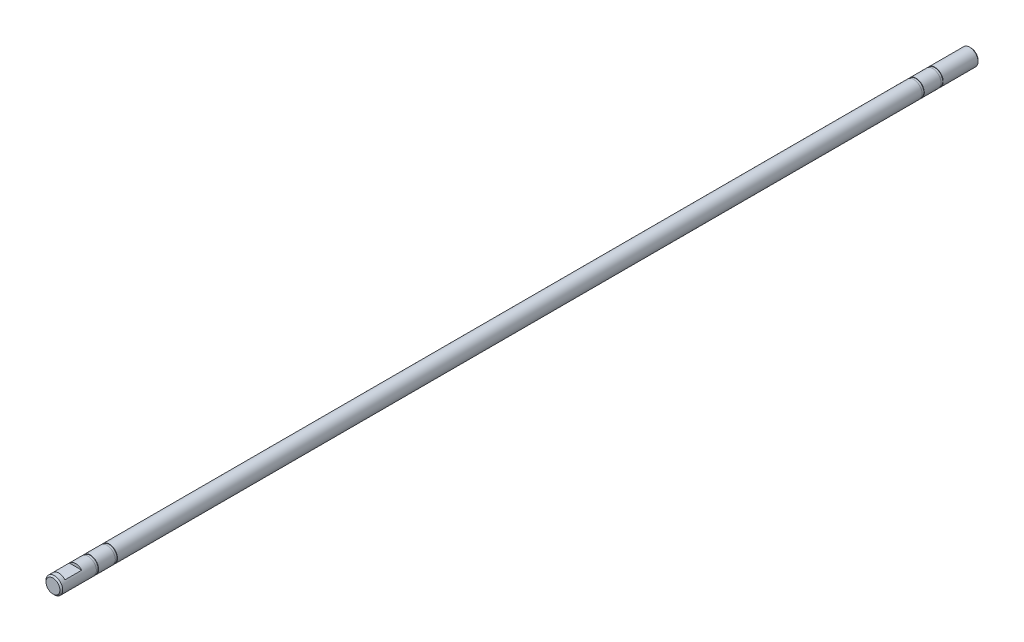
SolidWorks part; units mm, degrees
ref_plane "Front Plane" through (0, 0, 0) normal (0, 0, 1) x (1, 0, 0)
ref_plane "Top Plane" through (0, 0, 0) normal (0, 1, 0) x (1, 0, 0)
ref_plane "Right Plane" through (0, 0, 0) normal (1, 0, 0) x (0, 0, -1)
sketch "Sketch1" plane through (0, 0, 0) normal (0, 0, 1) x (1, 0, 0)
  circle A0 centre (0, 0) radius 3
  dimension "D1" = 6
extrude "Boss-Extrude1" add sketch "Sketch1" along normal blind 330
sketch "Sketch2" plane through (0, 0, 0) normal (0, 0, -1) x (-1, 0, 0)
  circle A0 centre (0, 0) radius 2.85
  circle A1 centre (0, 0) radius 3 construction
  circle A2 centre (0, 0) radius 3
  dimension "D1" = 5.7
extrude "Cut-Extrude1" cut sketch "Sketch2" against normal blind 0.8 from offset 13 offset against normal yes
sketch "Sketch3" plane through (0, 0, 13.8) normal (0, 0, -1) x (-1, 0, 0)
  circle A0 centre (0, 0) radius 3 construction
  circle A1 centre (0, 0) radius 2.85 construction
  circle A2 centre (0, 0) radius 3
  circle A3 centre (0, 0) radius 2.85
extrude "Cut-Extrude2" cut sketch "Sketch3" against normal blind 0.8 from offset 6 offset against normal yes
extrude "Cut-Extrude3" cut sketch "Sketch3<2>" against normal blind 0.8 from offset 296 offset against normal yes
sketch "Sketch3<2>" plane through (0, 0, 13.8) normal (0, 0, -1) x (-1, 0, 0) same geometry as "Sketch3"
extrude "Cut-Extrude4" cut sketch "Sketch3<3>" against normal blind 0.8 from offset 302.8 offset against normal yes
sketch "Sketch3<3>" plane through (0, 0, 13.8) normal (0, 0, -1) x (-1, 0, 0) same geometry as "Sketch3"
sketch "Sketch4" plane through (0, 0, 0) normal (0, 1, 0) x (1, 0, 0)
  line L0 (0, -317.4) -> (0, -321.9) construction
  line L1 (3, -317.4) -> (-3, -317.4) construction
  line L2 (-3, -317.4) -> (-3, -330) construction
  line L3 (-3, -321.9) -> (3, -321.9)
  line L4 (-3, -321.9) -> (-3, -327.9)
  line L5 (-3, -327.9) -> (3, -327.9)
  line L6 (3, -321.9) -> (3, -327.9)
  line L7 (3, -330) -> (3, -317.4) construction
  point P13 (0, 0)
  dimension "D1" = 4.5
  dimension "D2" = 6
extrude "Cut-Extrude5" cut sketch "Sketch4" against normal blind 1 from offset 3
chamfer "Chamfer1" distance 0.5 angle 45 2 edges at (3, 0, 0) (3, 0, 330)
